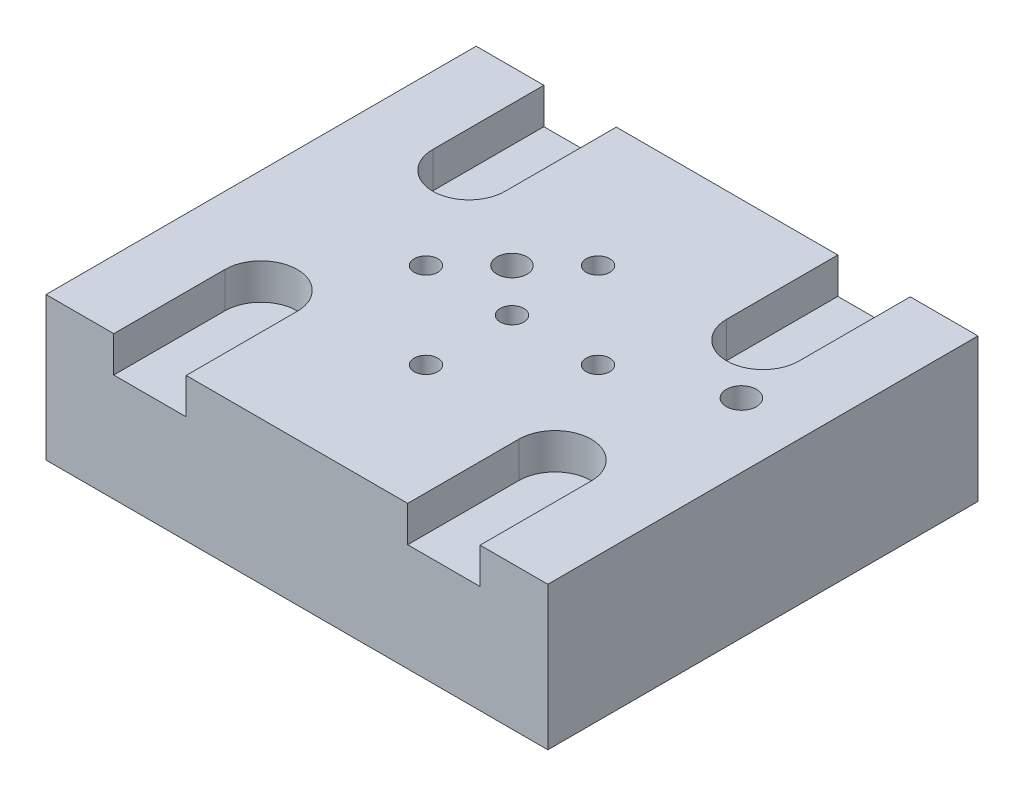
SolidWorks part; units mm, degrees
ref_plane "Front Plane" through (0, 0, 0) normal (0, 0, 1) x (1, 0, 0)
ref_plane "Top Plane" through (0, 0, 0) normal (0, 1, 0) x (1, 0, 0)
ref_plane "Right Plane" through (0, 0, 0) normal (1, 0, 0) x (0, 0, -1)
sketch "Sketch3" plane through (0, 0, 0) normal (0, 1, 0) x (1, 0, 0)
  line L1 (0, 0) -> (70, 0)
  line L2 (0, 0) -> (0, -60)
  line L3 (0, -60) -> (70, -60)
  line L4 (70, 0) -> (70, -60)
  dimension "D1" = 70
  dimension "D2" = 60
extrude "Boss-Extrude3" add sketch "Sketch3" along normal blind 20
sketch "Sketch4" plane through (0, 20, 0) normal (0, 1, 0) x (1, 0, 0)
  line L0 (35, 0) -> (35, -60) construction
  line L1 (70, 0) -> (0, 0) construction
  line L2 (0, -60) -> (70, -60) construction
  line L3 (0, -30) -> (70, -30) construction
  line L4 (0, 0) -> (0, -60) construction
  line L5 (70, -60) -> (70, 0) construction
  line L6 (21.35, -30) -> (21.35, 0) construction
  line L7 (0, 0) -> (70, 0) construction
  line L8 (24.65, -30) -> (24.65, 0) construction
  line L9 (45.35, -30) -> (45.35, 0) construction
  line L10 (48.65, -30) -> (48.65, 0) construction
  circle A0 centre (35, -30) radius 1.65
  circle A1 centre (35, -18) radius 1.65
  circle A2 centre (47, -30) radius 1.65
  circle A3 centre (35, -42) radius 1.65
  circle A4 centre (23, -30) radius 1.65
  dimension "D1" = 3.3
  dimension "D2" = 12
  dimension "D3" = 12
  dimension "D4" = 12
  dimension "D5" = 12
extrude "Cut-Extrude1" cut sketch "Sketch4" against normal through all
sketch "Sketch6" plane through (0, 0, 0) normal (0, -1, 0) x (1, 0, 0)
  line L0 (70, 30) -> (0, 30) construction
  line L1 (55, 24) -> (35, 24) construction
  line L2 (67, 24) -> (70, 24) construction
  line L3 (70, 60) -> (70, 0) construction
  line L4 (0, 0) -> (0, 60) construction
  line L5 (29, 24) -> (29, 0) construction
  line L6 (70, 0) -> (0, 0) construction
  line L7 (61, 24) -> (61, 0) construction
  line L8 (35, 24) -> (35, 0) construction
  line L9 (55, 24) -> (55, 0) construction
  line L10 (23, 24) -> (23, 0) construction
  line L11 (67, 24) -> (67, 0) construction
  line L12 (58.9, 24) -> (58.9, 0) construction
  line L13 (63.1, 24) -> (63.1, 0) construction
  line L14 (31.1, 24) -> (31.1, 0) construction
  line L15 (26.9, 24) -> (26.9, 0) construction
  line L16 (35, 0) -> (35, 60) construction
  line L17 (34.9322, 16.3514) -> (34.9322, 0) construction
  circle A2 centre (61, 24) radius 6 construction
  circle A3 centre (29, 24) radius 6 construction
  circle A4 centre (61, 24) radius 2.1
  circle A5 centre (29, 24) radius 2.1
  circle A6 centre (35, 18) radius 1.65 construction
  dimension "D1" = 12
  dimension "D2" = 20
  dimension "D3" = 4.2
extrude "Cut-Extrude2" cut sketch "Sketch6" against normal through all contours A4 | A5 region at (61, 0, 24)
sketch "Sketch9" plane through (0, 0, 0) normal (0, 0, -1) x (-1, 0, 0)
  line L0 (-29, 0) -> (-29, 20) construction
  line L1 (-70, 20) -> (0, 20) construction
  line L2 (-61, 0) -> (-61, 20) construction
  line L3 (-67, 0) -> (-55, 0) construction
  line L4 (-23, 0) -> (-23, 20) construction
  line L5 (-35, 0) -> (-35, 20) construction
  line L6 (-55, 0) -> (-55, 20) construction
  line L7 (-67, 0) -> (-67, 20) construction
  line L8 (-58.9, 0) -> (-58.9, 20) construction
  line L9 (-63.1, 0) -> (-63.1, 20) construction
  line L10 (-31.1, 0) -> (-31.1, 20) construction
  line L11 (-26.9, 0) -> (-26.9, 20) construction
  line L12 (-58.9, 7.5) -> (-56.45, 7.5) construction
  line L13 (-53.2, 10.75) -> (-53.2, 20) construction
  line L14 (-13.4822, 7.5) -> (0, 7.5) construction
  line L15 (-19.9822, 7.5) -> (-21.35, 7.5) construction
  line L16 (-16.7322, 20) -> (-16.7322, 10.75) construction
  line L17 (0, 20) -> (0, 0) construction
  line L18 (-34.9322, 0) -> (-34.9322, 20) construction
  line L19 (-34.9322, 0) -> (-34.9322, 20) construction
  line L20 (-49.95, 7.5) -> (-34.9322, 7.5) construction
  line L21 (-21.35, 20) -> (-21.35, 0) construction
  line L22 (0, 0) -> (-70, 0) construction
  line L23 (-24.65, 20) -> (-24.65, 0) construction
  line L24 (-45.35, 20) -> (-45.35, 0) construction
  line L25 (-48.65, 20) -> (-48.65, 0) construction
  line L26 (0, 7.5) -> (0, 20) construction
  circle A0 centre (-53.2, 7.5) radius 3.25
  circle A1 centre (-16.7322, 7.5) radius 3.25
  dimension "D1" = 6.5
  dimension "D2" = 18.2
  dimension "D3" = 18.2
  dimension "D4" = 12.5
extrude "Cut-Extrude3" cut sketch "Sketch9" against normal blind 40.25
sketch "Sketch11" plane through (0, 0, 0) normal (0, -1, 0) x (1, 0, 0)
  line L0 (70, 30) -> (0, 30) construction
  circle A0 centre (23, 30) radius 3
  circle A1 centre (35, 42) radius 3
  circle A2 centre (35, 30) radius 3
  circle A3 centre (35, 18) radius 3
  circle A4 centre (47, 30) radius 3
  circle M3 centre (35, 18) radius 1.65
  circle M4 centre (47, 30) radius 1.65
  circle M5 centre (35, 42) radius 1.65
  circle M6 centre (23, 30) radius 1.65
  circle M7 centre (35, 30) radius 1.65
  dimension "D1" = 6
extrude "Cut-Extrude4" cut sketch "Sketch11" against normal blind 3 contours A3 M3 | A2 M7 | A4 M4 | A0 M6 | A1 M5 | M5 | M6 | M7 | M4 | M3 | A3 region at (20.0849, 0, 30) region at (32.0849, 0, 42) region at (32.0849, 0, 30) region at (32.0849, 0, 18) region at (44.0849, 0, 30) region at (35, 0, 18) region at (47, 0, 30) region at (35, 0, 42) region at (23, 0, 30) region at (35, 0, 30)
chamfer "Chamfer1" distance 0.8 angle 45 2 edges at (49.95, 7.5, 0) (13.4822, 7.5, 0)
sketch "Sketch12" plane through (0, 20, 0) normal (0, 1, 0) x (1, 0, 0)
  line L0 (35, -60.1049) -> (14.5, -60.1049) construction
  line L1 (35, 0.1049) -> (35, -60.1049) construction
  line L2 (14.5, -60.1049) -> (14.5, -44.5) construction
  line L3 (9.45, -60.1049) -> (9.45, -44.5)
  line L4 (19.55, -60.1049) -> (19.55, -44.5)
  line L5 (70, -30) -> (0, -30) construction
  line L6 (35, 0) -> (35, -60) construction
  line L7 (35, 0.1049) -> (14.5, 0.1049) construction
  line L8 (55.5, -60.1049) -> (55.5, -44.5) construction
  line L9 (60.55, -60.1049) -> (60.55, -44.5)
  line L10 (50.45, -60.1049) -> (50.45, -44.5)
  line L11 (55.5, 0.1049) -> (55.5, -15.5) construction
  line L12 (60.55, 0.1049) -> (60.55, -15.5)
  line L13 (50.45, 0.1049) -> (50.45, -15.5)
  line L14 (14.5, 0.1049) -> (14.5, -15.5) construction
  line L15 (9.45, 0.1049) -> (9.45, -15.5)
  line L16 (19.55, 0.1049) -> (19.55, -15.5)
  arc A0 (9.45, -60.1049) -> (19.55, -60.1049) centre (14.5, -60.1049) ccw
  arc A1 (19.55, -44.5) -> (9.45, -44.5) centre (14.5, -44.5) ccw
  arc A3 (60.55, -60.1049) -> (50.45, -60.1049) centre (55.5, -60.1049) cw
  arc A4 (50.45, -44.5) -> (60.55, -44.5) centre (55.5, -44.5) cw
  arc A6 (60.55, 0.1049) -> (50.45, 0.1049) centre (55.5, 0.1049) ccw
  arc A7 (50.45, -15.5) -> (60.55, -15.5) centre (55.5, -15.5) ccw
  arc A8 (9.45, 0.1049) -> (19.55, 0.1049) centre (14.5, 0.1049) cw
  arc A9 (19.55, -15.5) -> (9.45, -15.5) centre (14.5, -15.5) cw
  point P0 (14.5, -52.3025)
  point P19 (35, -30)
  point P23 (55.5, -52.3025)
  point P29 (55.5, -7.6975)
  point P36 (14.5, -7.6975)
  dimension "D4" = 5.05
  dimension "D1" = 20.5
extrude "Cut-Extrude5" cut sketch "Sketch12" against normal blind 5
